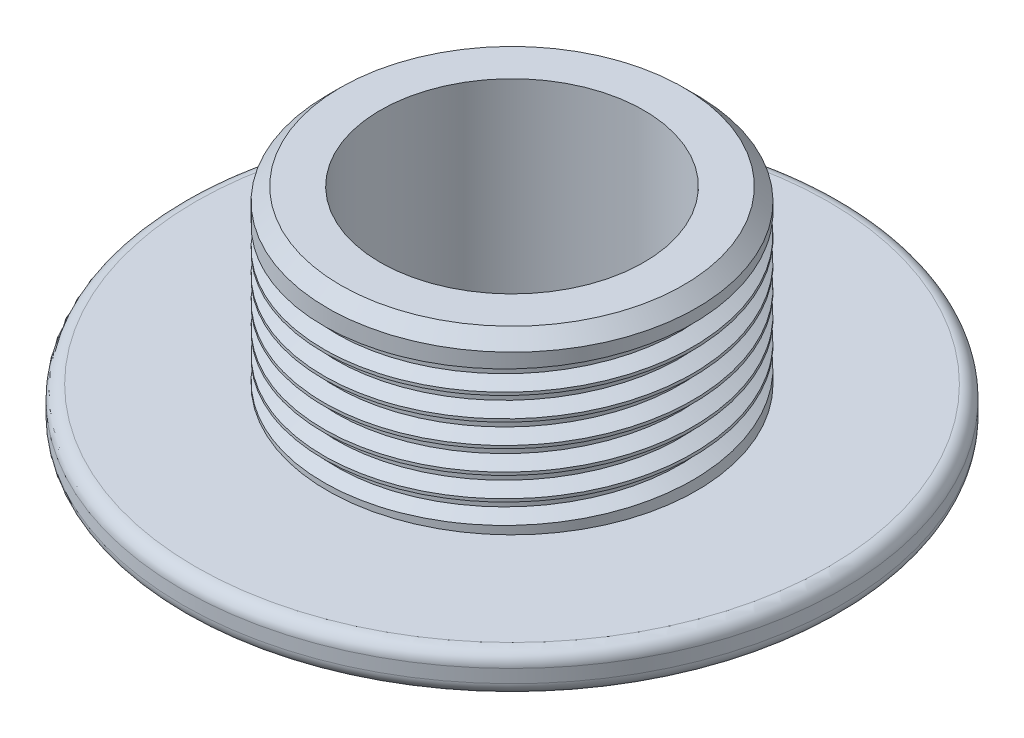
SolidWorks part; units mm, degrees
ref_plane "Front Plane" through (0, 0, 0) normal (0, 0, 1) x (1, 0, 0)
ref_plane "Top Plane" through (0, 0, 0) normal (0, 1, 0) x (1, 0, 0)
ref_plane "Right Plane" through (0, 0, 0) normal (1, 0, 0) x (0, 0, -1)
sketch "Sketch1" plane through (0, 0, 0) normal (0, 1, 0) x (1, 0, 0)
  circle A0 centre (0, 0) radius 25
  circle A1 centre (0, 0) radius 10
  dimension "D1" = 50
  dimension "D2" = 20
extrude "Boss-Extrude1" add sketch "Sketch1" along normal blind 3
sketch "Sketch2" plane through (0, 3, 0) normal (0, 1, 0) x (1, 0, 0)
  circle A0 centre (0, 0) radius 14
  circle A1 centre (0, 0) radius 10
  circle A2 centre (0, 0) radius 10 construction
  dimension "D1" = 28
extrude "Boss-Extrude2" add sketch "Sketch2" along normal blind 13
fillet "Fillet1" radius 1 2 edges at (0, 0, 25) (0, 3, 25)
chamfer "Chamfer1" distance 1 angle 45 1 edges at (0, 16, 14)
thread "Thread1" pitch 1.75 method cut trim with start face yes profile "Thread Profile1" start angle 0, offset 0, length 11, pitch 1.75, diameter 28
ref_plane "Plane1" through (-14, 15, 0) normal (0, 0, 1) x (-1, 0, 0)
sketch "Thread Profile1" plane through (-14, 15, 0) normal (0, 0, 1) x (-1, 0, 0)
  line L0 (0, 0) -> (0, 1.75) construction
  line L11 (0, 0) -> (0, 1.5312)
  line L12 (0, 1.5312) -> (-0.9472, 0.9844)
  line L13 (-0.9472, 0.9844) -> (-0.9472, 0.5469)
  line L15 (-0.9472, 0.5469) -> (0, 0)
  line L17 (-0.9472, 0.7656) -> (0, 0.7656) construction
  point P2 (0, 0)
  dimension "Pitch" = 1.75
  dimension "Profile_Angle" = 60
  dimension "Profile_Land" = 0.4375
  dimension "Profile_Height" = 0.9472
